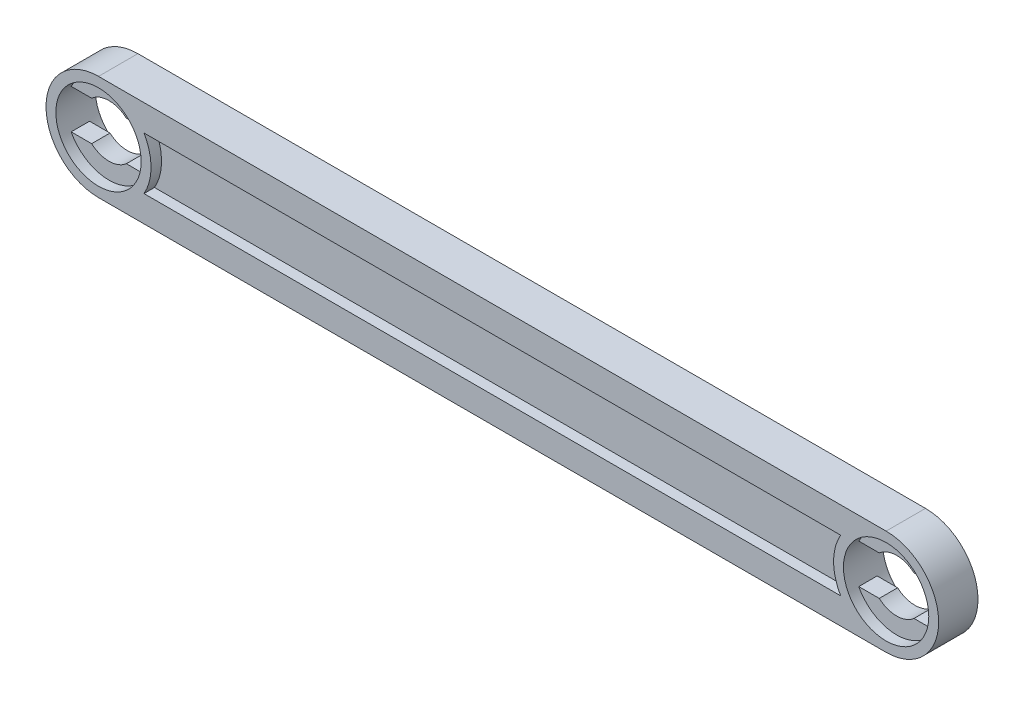
SolidWorks part; units mm, degrees
note: The reader was unsure of these and kept them because the rebuilt part matched: shared geometry of "草图3<2>".
ref_plane "前视基准面" through (0, 0, 0) normal (0, 0, 1) x (1, 0, 0)
ref_plane "上视基准面" through (0, 0, 0) normal (0, 1, 0) x (1, 0, 0)
ref_plane "右视基准面" through (0, 0, 0) normal (1, 0, 0) x (0, 0, -1)
sketch "草图1" plane through (0, 0, 0) normal (0, 0, 1) x (1, 0, 0)
  line L1 (0, 4) -> (60, 4)
  line L3 (0, -4) -> (60, -4)
  arc A0 (0, 4) -> (0, -4) centre (0, 0) ccw
  arc A1 (60, -4) -> (60, 4) centre (60, 0) ccw
extrude "凸台-拉伸1" add sketch "草图1" against normal blind 3
sketch "草图2" plane through (0, 0, 0) normal (0, 0, 1) x (1, 0, 0)
  line L0 (1.3229, -1.5) -> (2.8831, -1.5)
  line L1 (-2.8831, -1.5) -> (-1.3229, -1.5)
  line L2 (1.3229, 1.5) -> (2.8831, 1.5)
  line L3 (-2.8831, 1.5) -> (-1.3229, 1.5)
  arc A0 (1.3229, 1.5) -> (-1.3229, 1.5) centre (0, 0) ccw
  arc A1 (-2.8831, 1.5) -> (-2.8831, -1.5) centre (0, 0) ccw
  arc A3 (2.8831, -1.5) -> (2.8831, 1.5) centre (0, 0) ccw
  arc A4 (-1.3229, -1.5) -> (1.3229, -1.5) centre (0, 0) ccw
extrude "切除-拉伸1" cut sketch "草图2" against normal up to next
sketch "草图3" plane through (0, 0, 0) normal (0, 0, 1) x (1, 0, 0)
  circle A1 centre (0, 0) radius 3.25
extrude "切除-拉伸2" cut sketch "草图3" against normal blind 0.8
extrude "切除-拉伸3" cut sketch "草图3<2>" along normal blind 0.8 from offset 3 offset against normal yes
sketch "草图3<2>" plane through (0, 0, 0) normal (0, 0, 1) x (1, 0, 0) same geometry as "草图3"
ref_plane "基准面1" through (30, 0, 0) normal (1, 0, 0) x (0, 0, -1)
mirror "镜向1" about plane through (30, 0, 0) normal (1, 0, 0) of "切除-拉伸3", "切除-拉伸2", "切除-拉伸1"
sketch "草图4" plane through (0, 0, 0) normal (0, 0, 1) x (1, 0, 0)
  line L0 (3.4641, 2) -> (56.5359, 2)
  line L2 (3.4641, -2) -> (56.5359, -2)
  arc A0 (3.4641, -2) -> (3.4641, 2) centre (0, 0) ccw
  arc A2 (56.5359, 2) -> (56.5359, -2) centre (60, 0) ccw
extrude "切除-拉伸4" cut sketch "草图4" against normal blind 0.8
sketch "草图5" plane through (0, 0, -3) normal (0, 0, -1) x (-1, 0, 0)
  line L1 (-56, -2) -> (-4, -2)
  line L2 (-56, -2) -> (-56, 2)
  line L3 (-56, 2) -> (-4, 2)
  line L4 (-4, -2) -> (-4, 2)
extrude "切除-拉伸5" cut sketch "草图5" against normal blind 0.8
